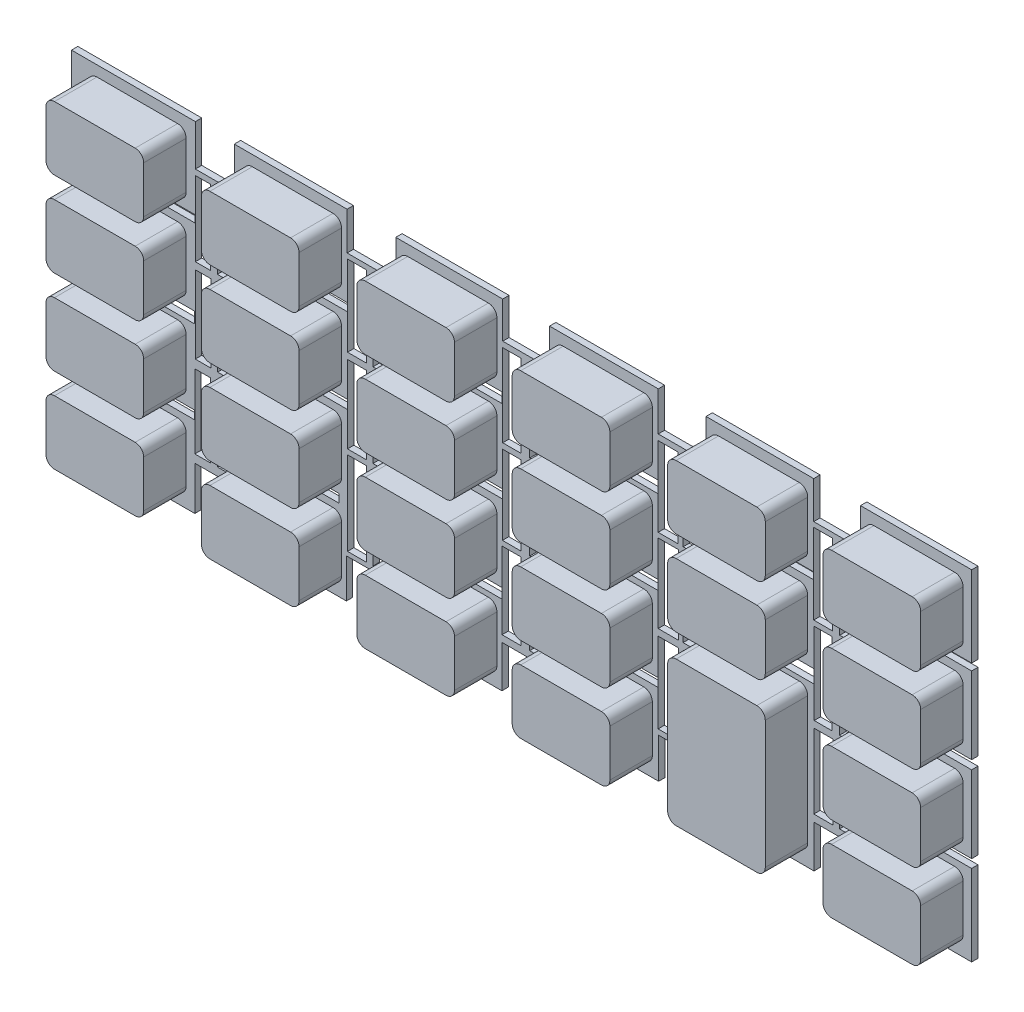
SolidWorks part; units mm, degrees
ref_plane "Front Plane" through (0, 0, 0) normal (0, 0, 1) x (1, 0, 0)
ref_plane "Top Plane" through (0, 0, 0) normal (0, 1, 0) x (1, 0, 0)
ref_plane "Right Plane" through (0, 0, 0) normal (1, 0, 0) x (0, 0, -1)
sketch "Sketch1" plane through (0, 0, 0) normal (0, 0, 1) x (1, 0, 0)
  line L1 (64.5, -22) -> (-64.5, -22)
  line L2 (64.5, -22) -> (64.5, 22)
  line L3 (64.5, 22) -> (-64.5, 22)
  line L4 (-64.5, -22) -> (-64.5, 22)
  line L5 (64.5, -22) -> (-64.5, 22) construction
  line L6 (64.5, 22) -> (-64.5, -22) construction
  point P0 (0, 0)
  dimension "D1" = 129
  dimension "D2" = 44
extrude "main_body" add sketch "Sketch1" along normal blind 0.75
sketch "Sketch2" plane through (0, 0, 0.75) normal (0, 0, 1) x (1, 0, 0)
  line L0 (46.25, 22) -> (46.25, -22) construction
  line L1 (64.5, 22) -> (-64.5, 22) construction
  line L2 (-64.5, -22) -> (64.5, -22) construction
  line L3 (64.5, -22) -> (64.5, 22) construction
  line L4 (36.95, -5) -> (36.95, -15) construction
  line L5 (27.95, -22) -> (27.95, 22) construction
  line L6 (-64.5, 22) -> (-64.5, -22) construction
  line L7 (-39.5, 11.25) -> (-51, 11.25)
  line L8 (9.65, 22) -> (9.65, -22) construction
  line L9 (-39.5, 1.25) -> (-51, 1.25)
  line L10 (64.5, 5) -> (-64.5, 5) construction
  line L11 (-8.65, -22) -> (-8.65, 22) construction
  line L12 (-39.5, 1.25) -> (-39.5, 8.75)
  line L13 (-39.5, 8.75) -> (-51, 8.75)
  line L14 (-26.95, 22) -> (-26.95, -22) construction
  line L15 (-64.5, 15) -> (64.5, 15) construction
  line L16 (-51, 1.25) -> (-51, 8.75)
  line L17 (-45.25, -22) -> (-45.25, 22) construction
  line L18 (-39.5, 1.25) -> (-51, 8.75) construction
  line L19 (64.5, -5) -> (-64.5, -5) construction
  line L20 (-39.5, 8.75) -> (-51, 1.25) construction
  line L21 (-21.2, 1.25) -> (-32.7, 1.25)
  line L22 (-64.5, -15) -> (64.5, -15) construction
  line L23 (-21.2, 1.25) -> (-21.2, 8.75)
  line L24 (-21.2, 8.75) -> (-32.7, 8.75)
  line L25 (-32.7, 1.25) -> (-32.7, 8.75)
  line L26 (-21.2, 1.25) -> (-32.7, 8.75) construction
  line L27 (-21.2, 8.75) -> (-32.7, 1.25) construction
  line L28 (-2.9, 1.25) -> (-14.4, 1.25)
  line L29 (-2.9, 1.25) -> (-2.9, 8.75)
  line L30 (-2.9, 8.75) -> (-14.4, 8.75)
  line L31 (-14.4, 1.25) -> (-14.4, 8.75)
  line L32 (-2.9, 1.25) -> (-14.4, 8.75) construction
  line L33 (-2.9, 8.75) -> (-14.4, 1.25) construction
  line L34 (15.4, 1.25) -> (3.9, 1.25)
  line L35 (15.4, 1.25) -> (15.4, 8.75)
  line L36 (15.4, 8.75) -> (3.9, 8.75)
  line L37 (3.9, 1.25) -> (3.9, 8.75)
  line L38 (15.4, 1.25) -> (3.9, 8.75) construction
  line L39 (15.4, 8.75) -> (3.9, 1.25) construction
  line L40 (33.7, 1.25) -> (22.2, 1.25)
  line L41 (33.7, 1.25) -> (33.7, 8.75)
  line L42 (33.7, 8.75) -> (22.2, 8.75)
  line L43 (22.2, 1.25) -> (22.2, 8.75)
  line L44 (33.7, 1.25) -> (22.2, 8.75) construction
  line L45 (33.7, 8.75) -> (22.2, 1.25) construction
  line L46 (52, -8.75) -> (40.5, -8.75)
  line L47 (52, -8.75) -> (52, -1.25)
  line L48 (52, -1.25) -> (40.5, -1.25)
  line L49 (40.5, -8.75) -> (40.5, -1.25)
  line L50 (52, -8.75) -> (40.5, -1.25) construction
  line L51 (52, -1.25) -> (40.5, -8.75) construction
  line L52 (52, -18.75) -> (40.5, -18.75)
  line L53 (52, -18.75) -> (52, -11.25)
  line L54 (52, -11.25) -> (40.5, -11.25)
  line L55 (40.5, -18.75) -> (40.5, -11.25)
  line L56 (52, -18.75) -> (40.5, -11.25) construction
  line L57 (52, -11.25) -> (40.5, -18.75) construction
  line L58 (52, 11.25) -> (40.5, 11.25)
  line L59 (52, 11.25) -> (52, 18.75)
  line L60 (52, 18.75) -> (40.5, 18.75)
  line L61 (40.5, 11.25) -> (40.5, 18.75)
  line L62 (52, 11.25) -> (40.5, 18.75) construction
  line L63 (52, 18.75) -> (40.5, 11.25) construction
  line L64 (-39.5, 11.25) -> (-39.5, 18.75)
  line L65 (-39.5, 18.75) -> (-51, 18.75)
  line L66 (-51, 11.25) -> (-51, 18.75)
  line L67 (-39.5, 11.25) -> (-51, 18.75) construction
  line L68 (-39.5, 18.75) -> (-51, 11.25) construction
  line L69 (-39.5, -8.75) -> (-51, -8.75)
  line L70 (-39.5, -8.75) -> (-39.5, -1.25)
  line L71 (-39.5, -1.25) -> (-51, -1.25)
  line L72 (-51, -8.75) -> (-51, -1.25)
  line L73 (-39.5, -8.75) -> (-51, -1.25) construction
  line L74 (-39.5, -1.25) -> (-51, -8.75) construction
  line L75 (-39.5, -18.75) -> (-51, -18.75)
  line L76 (-39.5, -18.75) -> (-39.5, -11.25)
  line L77 (-39.5, -11.25) -> (-51, -11.25)
  line L78 (-51, -18.75) -> (-51, -11.25)
  line L79 (-39.5, -18.75) -> (-51, -11.25) construction
  line L80 (-39.5, -11.25) -> (-51, -18.75) construction
  line L81 (-21.2, 11.25) -> (-32.7, 11.25)
  line L82 (-21.2, 11.25) -> (-21.2, 18.75)
  line L83 (-21.2, 18.75) -> (-32.7, 18.75)
  line L84 (-32.7, 11.25) -> (-32.7, 18.75)
  line L85 (-21.2, 11.25) -> (-32.7, 18.75) construction
  line L86 (-21.2, 18.75) -> (-32.7, 11.25) construction
  line L87 (-21.2, -8.75) -> (-32.7, -8.75)
  line L88 (-21.2, -8.75) -> (-21.2, -1.25)
  line L89 (-21.2, -1.25) -> (-32.7, -1.25)
  line L90 (-32.7, -8.75) -> (-32.7, -1.25)
  line L91 (-21.2, -8.75) -> (-32.7, -1.25) construction
  line L92 (-21.2, -1.25) -> (-32.7, -8.75) construction
  line L93 (-21.2, -18.75) -> (-32.7, -18.75)
  line L94 (-21.2, -18.75) -> (-21.2, -11.25)
  line L95 (-21.2, -11.25) -> (-32.7, -11.25)
  line L96 (-32.7, -18.75) -> (-32.7, -11.25)
  line L97 (-21.2, -18.75) -> (-32.7, -11.25) construction
  line L98 (-21.2, -11.25) -> (-32.7, -18.75) construction
  line L99 (-2.9, -8.75) -> (-14.4, -8.75)
  line L100 (-2.9, -8.75) -> (-2.9, -1.25)
  line L101 (-2.9, -1.25) -> (-14.4, -1.25)
  line L102 (-14.4, -8.75) -> (-14.4, -1.25)
  line L103 (-2.9, -8.75) -> (-14.4, -1.25) construction
  line L104 (-2.9, -1.25) -> (-14.4, -8.75) construction
  line L105 (-2.9, -18.75) -> (-14.4, -18.75)
  line L106 (-2.9, -18.75) -> (-2.9, -11.25)
  line L107 (-2.9, -11.25) -> (-14.4, -11.25)
  line L108 (-14.4, -18.75) -> (-14.4, -11.25)
  line L109 (-2.9, -18.75) -> (-14.4, -11.25) construction
  line L110 (-2.9, -11.25) -> (-14.4, -18.75) construction
  line L111 (-2.9, 11.25) -> (-14.4, 11.25)
  line L112 (-2.9, 11.25) -> (-2.9, 18.75)
  line L113 (-2.9, 18.75) -> (-14.4, 18.75)
  line L114 (-14.4, 11.25) -> (-14.4, 18.75)
  line L115 (-2.9, 11.25) -> (-14.4, 18.75) construction
  line L116 (-2.9, 18.75) -> (-14.4, 11.25) construction
  line L117 (15.4, 11.25) -> (3.9, 11.25)
  line L118 (15.4, 11.25) -> (15.4, 18.75)
  line L119 (15.4, 18.75) -> (3.9, 18.75)
  line L120 (3.9, 11.25) -> (3.9, 18.75)
  line L121 (15.4, 11.25) -> (3.9, 18.75) construction
  line L122 (15.4, 18.75) -> (3.9, 11.25) construction
  line L123 (15.4, -8.75) -> (3.9, -8.75)
  line L124 (15.4, -8.75) -> (15.4, -1.25)
  line L125 (15.4, -1.25) -> (3.9, -1.25)
  line L126 (3.9, -8.75) -> (3.9, -1.25)
  line L127 (15.4, -8.75) -> (3.9, -1.25) construction
  line L128 (15.4, -1.25) -> (3.9, -8.75) construction
  line L129 (15.4, -18.75) -> (3.9, -18.75)
  line L130 (15.4, -18.75) -> (15.4, -11.25)
  line L131 (15.4, -11.25) -> (3.9, -11.25)
  line L132 (3.9, -18.75) -> (3.9, -11.25)
  line L133 (15.4, -18.75) -> (3.9, -11.25) construction
  line L134 (15.4, -11.25) -> (3.9, -18.75) construction
  line L135 (33.7, 11.25) -> (22.2, 11.25)
  line L136 (33.7, 11.25) -> (33.7, 18.75)
  line L137 (33.7, 18.75) -> (22.2, 18.75)
  line L138 (22.2, 11.25) -> (22.2, 18.75)
  line L139 (33.7, 11.25) -> (22.2, 18.75) construction
  line L140 (33.7, 18.75) -> (22.2, 11.25) construction
  line L141 (52, 1.25) -> (40.5, 1.25)
  line L142 (52, 1.25) -> (52, 8.75)
  line L143 (52, 8.75) -> (40.5, 8.75)
  line L144 (40.5, 1.25) -> (40.5, 8.75)
  line L145 (52, 1.25) -> (40.5, 8.75) construction
  line L146 (52, 8.75) -> (40.5, 1.25) construction
  line L147 (36.95, -10) -> (27.95, -10) construction
  line L149 (33.7, -18.5) -> (22.2, -18.5)
  line L150 (33.7, -18.5) -> (33.7, -1.5)
  line L151 (33.7, -1.5) -> (22.2, -1.5)
  line L152 (22.2, -18.5) -> (22.2, -1.5)
  line L153 (33.7, -18.5) -> (22.2, -1.5) construction
  line L154 (33.7, -1.5) -> (22.2, -18.5) construction
  point P13 (-45.25, 15)
  point P23 (-45.25, 5)
  point P35 (-26.95, 5)
  point P40 (-8.65, 5)
  point P45 (9.65, 5)
  point P50 (27.95, 5)
  point P55 (46.25, -5)
  point P60 (46.25, -15)
  point P65 (46.25, 15)
  point P70 (-45.25, -5)
  point P75 (-45.25, -15)
  point P80 (-26.95, 15)
  point P88 (-26.95, -5)
  point P93 (-26.95, -15)
  point P98 (-8.65, -15)
  point P100 (-8.65, -5)
  point P108 (-8.65, 15)
  point P113 (9.65, 15)
  point P118 (9.65, -5)
  point P123 (9.65, -15)
  point P128 (27.95, 15)
  point P133 (46.25, 5)
  point P142 (27.95, -10)
  dimension "D1" = 18.25
  dimension "D3" = 18.3
  dimension "D4" = 18.3
  dimension "D5" = 18.3
  dimension "D6" = 18.3
  dimension "D7" = 10
  dimension "D8" = 7
  dimension "D9" = 10
  dimension "D10" = 10
  dimension "D11" = 11.5
  dimension "D12" = 11.5
  dimension "D13" = 11.5
  dimension "D14" = 11.5
  dimension "D15" = 7.5
  dimension "D16" = 7.5
  dimension "D17" = 7.5
  dimension "D18" = 7.5
  dimension "D19" = 7.5
  dimension "D20" = 7.5
  dimension "D21" = 11.5
  dimension "D22" = 11.5
  dimension "D23" = 7.5
  dimension "D24" = 11.5
  dimension "D25" = 11.5
  dimension "D26" = 7.5
  dimension "D27" = 7
  dimension "D28" = 18.3
  dimension "D29" = 19.25
  dimension "D30" = 9
  dimension "D31" = 5
  dimension "D32" = 5
  dimension "D33" = 11.5
  dimension "D34" = 7.5
  dimension "D35" = 11.5
  dimension "D36" = 7.5
  dimension "D37" = 11.5
  dimension "D38" = 7.5
  dimension "D39" = 11.5
  dimension "D40" = 7.5
  dimension "D41" = 11.5
  dimension "D42" = 7.5
  dimension "D43" = 11.5
  dimension "D44" = 7.5
  dimension "D45" = 11.5
  dimension "D46" = 17
  dimension "D47" = 11.5
  dimension "D48" = 7.5
  dimension "D49" = 11.5
  dimension "D50" = 7.5
  dimension "D51" = 11.5
  dimension "D52" = 11.5
  dimension "D53" = 11.5
  dimension "D54" = 11.5
  dimension "D55" = 11.5
  dimension "D56" = 11.5
  dimension "D57" = 7.5
  dimension "D58" = 7.5
  dimension "D59" = 7.5
  dimension "D60" = 7.5
  dimension "D61" = 7.5
  dimension "D62" = 7.5
extrude "button_bumps" add sketch "Sketch2" along normal blind 5
fillet "button_corners" [suppressed] radius 1
fillet "button_top" [suppressed] radius 1
sketch "Sketch3" [suppressed] plane through (0, 0, 5.5) normal (0, 0, 1) x (1, 0, 0)
  line L0 (-50.5, 22) -> (-50.5, -22) construction
  line L1 (61.5, 22) -> (-61.5, 22) construction
  line L2 (-61.5, -22) -> (61.5, -22) construction
  line L3 (-32.2, 22) -> (-32.2, -22) construction
  line L4 (64.5, -19) -> (64.5, 19) construction
  line L5 (-52.25, 14.5) -> (-38.25, 14.5) construction
  line L6 (-52.25, 18) -> (-52.25, 12) construction
  line L7 (-13.9, 22) -> (-13.9, -22) construction
  line L8 (-38.25, 12) -> (-38.25, 18) construction
  line L9 (2.65, -12) -> (2.65, -18) construction
  line L10 (20.95, -2.5) -> (20.95, -17.5) construction
  line L11 (39.25, -12) -> (39.25, -18) construction
  line L12 (-15.65, -12) -> (-15.65, -18) construction
  line L13 (4.4, -22) -> (4.4, 22) construction
  line L14 (-33.95, -12) -> (-33.95, -18) construction
  line L15 (-52.25, -12) -> (-52.25, -18) construction
  line L16 (22.7, 22) -> (22.7, -22) construction
  line L17 (-64.5, 13.5) -> (64.5, 13.5) construction
  line L18 (-64.5, 19) -> (-64.5, -19) construction
  line L19 (41, -22) -> (41, 22) construction
  line L20 (-64.5, 3.5) -> (64.5, 3.5) construction
  line L21 (-52.25, 4.5) -> (-38.25, 4.5) construction
  line L22 (-52.25, 8) -> (-52.25, 2) construction
  line L23 (-64.5, -6.5) -> (64.5, -6.5) construction
  line L24 (-38.25, 2) -> (-38.25, 8) construction
  line L25 (-52.25, -15.5) -> (-38.25, -15.5) construction
  line L26 (64.5, -16.5) -> (-64.5, -16.5) construction
  line L27 (-52.25, -12) -> (-52.25, -18) construction
  line L28 (-38.25, -8) -> (-38.25, -2) construction
  line L29 (-38.25, -5.5) -> (-52.25, -5.5) construction
  line L30 (-52.25, -2) -> (-52.25, -8) construction
  line L31 (-38.25, -18) -> (-38.25, -12) construction
  line L32 (-33.95, 12.5) -> (34.95, 12.5) construction
  line L33 (-33.95, 18) -> (-33.95, 12) construction
  line L34 (34.95, 12) -> (34.95, 18) construction
  line L35 (-33.95, 2.5) -> (34.95, 2.5) construction
  line L36 (-21.35, 19) -> (-21.35, -19) construction
  line L37 (-20.95, 19) -> (-32.95, 19) construction
  line L38 (-33.95, 8) -> (-33.95, 2) construction
  line L39 (34.95, 2) -> (34.95, 8) construction
  line L40 (-32.95, -19) -> (-20.95, -19) construction
  line L41 (-33.95, -7.5) -> (34.95, -7.5) construction
  line L42 (-19.95, -18) -> (-19.95, -12) construction
  line L43 (-33.95, -2) -> (-33.95, -8) construction
  line L44 (34.95, -17.5) -> (34.95, -2.5) construction
  line L45 (-3.05, 19) -> (-3.05, -19) construction
  line L46 (-33.95, -17.5) -> (34.95, -17.5) construction
  line L47 (-2.65, 19) -> (-14.65, 19) construction
  line L48 (-14.65, -19) -> (-2.65, -19) construction
  line L49 (-33.95, -12) -> (-33.95, -18) construction
  line L50 (-33.95, 15.3) -> (34.95, 15.3) construction
  line L51 (-33.95, 5.3) -> (34.95, 5.3) construction
  line L52 (-33.95, -4.7) -> (34.95, -4.7) construction
  line L53 (-33.95, -14.7) -> (34.95, -14.7) construction
  line L54 (-1.65, -18) -> (-1.65, -12) construction
  line L55 (-4.6, -14.55) -> (-3.2, -14.55)
  line L56 (15.25, 19) -> (15.25, -19) construction
  line L57 (-3.05, -14.7) -> (-4.75, -14.7)
  line L58 (15.65, 19) -> (3.65, 19) construction
  line L59 (-3.05, -14.7) -> (-3.05, -14.55)
  line L60 (3.65, -19) -> (15.65, -19) construction
  line L62 (33.55, 19) -> (33.55, -18.5) construction
  line L63 (33.95, 19) -> (21.95, 19) construction
  line L64 (21.95, -18.5) -> (33.95, -18.5) construction
  line L65 (16.65, -18) -> (16.65, -12) construction
  line L66 (34.95, -17.5) -> (34.95, -2.5) construction
  line L67 (-4.75, -14.7) -> (-4.75, -14.55)
  line L69 (-4.75, -14.55) -> (-4.75, -14.4)
  line L70 (-4.75, -14.4) -> (-4.6, -14.4)
  line L71 (-4.6, -14.55) -> (-4.6, -14.4)
  line L73 (-3.05, -14.55) -> (-3.05, -14.4)
  line L74 (-3.05, -14.4) -> (-3.2, -14.4)
  line L75 (-3.2, -14.55) -> (-3.2, -14.4)
  line L76 (39.25, 13.8) -> (53.25, 13.8) construction
  line L77 (39.25, 18) -> (39.25, 12) construction
  line L78 (53.25, 12) -> (53.25, 18) construction
  line L79 (39.25, 3.8) -> (53.25, 3.8) construction
  line L80 (39.25, 8) -> (39.25, 2) construction
  line L81 (53.25, 2) -> (53.25, 8) construction
  line L82 (39.25, -6.2) -> (53.25, -6.2) construction
  line L83 (39.25, -2) -> (39.25, -8) construction
  line L84 (53.25, -8) -> (53.25, -2) construction
  line L85 (39.25, -16.2) -> (53.25, -16.2) construction
  line L86 (39.25, -12) -> (39.25, -18) construction
  line L87 (53.25, -18) -> (53.25, -12) construction
  line L88 (-52.25, 12.5) -> (-38.25, 12.5) construction
  line L89 (-52.25, 18) -> (-52.25, 12) construction
  line L90 (-38.25, 12) -> (-38.25, 18) construction
  line L91 (-52.25, 2.5) -> (-38.25, 2.5) construction
  line L92 (-52.25, -7.5) -> (-38.25, -7.5) construction
  line L93 (-52.25, -17.5) -> (-38.25, -17.5) construction
  text T0 "1" font "Arial Narrow" height in points 14
  text T1 "SSB" font "Arial Narrow" height in points 10
  text T2 "4" font "Arial Narrow" height in points 14
  text T3 "2" font "Arial Narrow" height in points 14
  text T4 "3" font "Arial Narrow" height in points 14
  text T5 "5" font "Arial Narrow" height in points 14
  text T6 "6" font "Arial Narrow" height in points 14
  text T7 "7" font "Arial Narrow" height in points 14
  text T8 "8" font "Arial Narrow" height in points 14
  text T9 "9" font "Arial Narrow" height in points 14
  text T10 "." font "Arial Rounded MT Bold" height in points 14
  text T11 "0" font "Arial Narrow" height in points 14
  text T12 "C" font "Arial Narrow" height in points 14
  text T13 "M" font "Arial Narrow" height in points 14
  text T14 "S" font "Arial Narrow" height in points 14
  text T15 "CW" font "Arial Narrow" height in points 10
  text T16 "AM" font "Arial Narrow" height in points 10
  text T17 "FIX" font "Arial Narrow" height in points 10
  text T18 "             160m" font "Arial Narrow" height in points 6
  text T19 "               30m" font "Arial Narrow" height in points 6
  text T20 "               12m" font "Arial Narrow" height in points 6
  text T21 "                 4m" font "Arial Narrow" height in points 6
  text T22 "               80m" font "Arial Narrow" height in points 6
  text T23 "               20m" font "Arial Narrow" height in points 6
  text T24 "               10m" font "Arial Narrow" height in points 6
  text T25 "                  LF" font "Arial Narrow" height in points 6
  text T26 "               60m" font "Arial Narrow" height in points 6
  text T27 "               17m" font "Arial Narrow" height in points 6
  text T28 "                 6m" font "Arial Narrow" height in points 6
  text T29 "                 MF" font "Arial Narrow" height in points 6
  text T30 "               40m" font "Arial Narrow" height in points 6
  text T31 "               15m" font "Arial Narrow" height in points 6
  text T32 "          ENTER" font "Arial Narrow" height in points 6
  text T33 "           ABC" font "Arial Narrow" height in points 7
  text T34 "           DEF" font "Arial Narrow" height in points 7
  text T35 "            GHI" font "Arial Narrow" height in points 7
  text T36 "             JKL" font "Arial Narrow" height in points 7
  text T37 "          MNO" font "Arial Narrow" height in points 7
  text T38 "         PQRS" font "Arial Narrow" height in points 7
  text T39 "           TUV" font "Arial Narrow" height in points 7
  text T40 "        WXYZ" font "Arial Narrow" height in points 7
  text T41 "              */--" font "Arial Narrow" height in points 7
  text T42 "         ↵" font "Lucida Sans Unicode" height in points 7
  text T43 "   DSP" font "Arial Narrow" height in points 10
  text T44 "  STEP" font "Arial Narrow" height in points 10
  text T45 "FILTER" font "Arial Narrow" height in points 10
  text T46 "  SPLIT" font "Arial Narrow" height in points 10
  text T47 "                   LSB/USB" font "Arial Narrow" height in points 4
  text T48 "                      KEYER" font "Arial Narrow" height in points 4
  text T49 "                    FM/DIGI" font "Arial Narrow" height in points 4
  text T50 "                   CENTER" font "Arial Narrow" height in points 4
  dimension "D1" = 23.5
  dimension "D2" = 18.3
  dimension "D3" = 18.3
  dimension "D4" = 18.3
  dimension "D5" = 18.3
  dimension "D6" = 18.3
  dimension "D7" = 1.75
  dimension "D8" = 1.75
  dimension "D9" = 1.75
  dimension "D10" = 1.75
  dimension "D11" = 1.75
  dimension "D12" = 1.75
  dimension "D13" = 10
  dimension "D14" = 10
  dimension "D15" = 10
  dimension "D16" = 8.5
  dimension "D17" = 5.5
  dimension "D18" = 1
  dimension "D19" = 1
  dimension "D20" = 1
  dimension "D21" = 1
  dimension "D22" = 1
  dimension "D23" = 1
  dimension "D24" = 1
  dimension "D25" = 1
  dimension "D26" = 1.8
  dimension "D27" = 1.8
  dimension "D28" = 1.8
  dimension "D29" = 1.8
  dimension "D30" = 1.4
  dimension "D31" = 1.4
  dimension "D32" = 1.4
  dimension "D33" = 1.4
  dimension "D34" = 1.7
  dimension "D35" = 0.15
  dimension "D36" = 0.3
  dimension "D37" = 0.15
  dimension "D38" = 0.15
  dimension "D39" = 0.15
  dimension "D40" = 0.15
  dimension "D41" = 0.15
  dimension "D42" = 0.15
  dimension "D43" = 0.3
  dimension "D44" = 0.3
  dimension "D45" = 0.3
  dimension "D46" = 1
  dimension "D47" = 1
  dimension "D48" = 1
  dimension "D49" = 1
extrude "buttons_text" [suppressed] add sketch "Sketch3" along normal blind 0.1
sketch "Sketch5" plane through (0, 0, 0.75) normal (0, 0, 1) x (1, 0, 0)
  line L62 (-53, 20) -> (53, 20)
  line L63 (-53, 20) -> (-53, -20)
  line L64 (-53, -20) -> (53, -20)
  line L65 (53, 20) -> (53, -20)
  dimension "D1" = 106
  dimension "D2" = 40
  dimension "D3" = 20
  dimension "D4" = 53
extrude "corners_cut" cut sketch "Sketch5" against normal through all flip side to cut
sketch "Sketch6" plane through (0, 0, 0.75) normal (0, 0, 1) x (1, 0, 0)
  line L0 (-53, 20) -> (-53, -20) construction
  line L1 (-53, 10.487) -> (-38.4318, 10.487)
  line L2 (-53, 10.487) -> (-53, 9.639)
  line L3 (-53, 9.639) -> (-38.4318, 9.639)
  line L4 (-38.4318, 10.487) -> (-38.4318, 9.639)
  line L5 (53, 20) -> (-53, 20) construction
  line L6 (-53, 0.6278) -> (-38.5268, 0.6278)
  line L7 (-53, 0.6278) -> (-53, -0.6772)
  line L8 (-53, -0.6772) -> (-38.5268, -0.6772)
  line L9 (-38.5268, 0.6278) -> (-38.5268, -0.6772)
  line L10 (-53, -9.4645) -> (-38.4947, -9.4645)
  line L11 (-53, -9.4645) -> (-53, -10.4595)
  line L12 (-53, -10.4595) -> (-38.4947, -10.4595)
  line L13 (-38.4947, -9.4645) -> (-38.4947, -10.4595)
  line L14 (-38.4124, 20) -> (-33.8283, 20)
  line L15 (-38.4124, 20) -> (-38.4124, 15.1621)
  line L16 (-38.4124, 15.1621) -> (-33.8283, 15.1621)
  line L17 (-33.8283, 20) -> (-33.8283, 15.1621)
  line L18 (-53, -20) -> (53, -20) construction
  line L23 (53, -20) -> (53, 20) construction
  line L24 (-20.5465, 20) -> (-14.8109, 20)
  line L25 (-20.5465, 20) -> (-20.5465, 15.5362)
  line L26 (-20.5465, 15.5362) -> (-14.8109, 15.5362)
  line L27 (-14.8109, 20) -> (-14.8109, 15.5362)
  line L28 (-2.2207, 20) -> (3.2938, 20)
  line L29 (-2.2207, 20) -> (-2.2207, 15.7023)
  line L30 (-2.2207, 15.7023) -> (3.2938, 15.7023)
  line L31 (3.2938, 20) -> (3.2938, 15.7023)
  line L32 (16.0959, 20) -> (21.7218, 20)
  line L33 (16.0959, 20) -> (16.0959, 15.3985)
  line L34 (16.0959, 15.3985) -> (21.7218, 15.3985)
  line L35 (21.7218, 20) -> (21.7218, 15.3985)
  line L36 (34.4017, 20) -> (39.911, 20)
  line L37 (34.4017, 20) -> (34.4017, 15.6134)
  line L38 (34.4017, 15.6134) -> (39.911, 15.6134)
  line L39 (39.911, 20) -> (39.911, 15.6134)
  line L40 (-20.6305, -20) -> (-15.0655, -20)
  line L41 (-20.6305, -20) -> (-20.6305, -15.3916)
  line L42 (-20.6305, -15.3916) -> (-15.0655, -15.3916)
  line L43 (-15.0655, -20) -> (-15.0655, -15.3916)
  line L44 (-2.3118, -20) -> (3.1497, -20)
  line L45 (-2.3118, -20) -> (-2.3118, -15.0585)
  line L46 (-2.3118, -15.0585) -> (3.1497, -15.0585)
  line L47 (3.1497, -20) -> (3.1497, -15.0585)
  line L48 (16.1416, -20) -> (21.3808, -20)
  line L49 (16.1416, -20) -> (16.1416, -15.2957)
  line L50 (16.1416, -15.2957) -> (21.3808, -15.2957)
  line L51 (21.3808, -20) -> (21.3808, -15.2957)
  line L52 (34.4363, -20) -> (39.9725, -20)
  line L53 (34.4363, -20) -> (34.4363, -15.0209)
  line L54 (34.4363, -15.0209) -> (39.9725, -15.0209)
  line L55 (39.9725, -20) -> (39.9725, -15.0209)
  line L61 (53, 0.6278) -> (40.0214, 0.6278)
  line L62 (53, 0.6278) -> (53, -0.4027)
  line L63 (53, -0.4027) -> (40.0214, -0.4027)
  line L64 (40.0214, 0.6278) -> (40.0214, -0.4027)
  line L65 (53, 10.487) -> (39.968, 10.487)
  line L66 (53, 10.487) -> (53, 9.6837)
  line L67 (53, 9.6837) -> (39.968, 9.6837)
  line L68 (39.968, 10.487) -> (39.968, 9.6837)
  line L73 (-38.4124, 14.5006) -> (-36.6167, 14.5006)
  line L74 (-38.4124, 14.5006) -> (-38.4124, 5.7068)
  line L75 (-38.4124, 5.7068) -> (-36.6167, 5.7068)
  line L76 (-36.6167, 14.5006) -> (-36.6167, 5.7068)
  line L81 (-38.4755, -13.9249) -> (-36.6481, -13.9249)
  line L82 (-38.4755, -13.9249) -> (-38.4755, -5.2376)
  line L83 (-38.4755, -5.2376) -> (-36.6481, -5.2376)
  line L84 (-36.6481, -13.9249) -> (-36.6481, -5.2376)
  line L97 (-38.4237, 4.89) -> (-36.5843, 4.89)
  line L98 (-38.4237, 4.89) -> (-38.4237, -4.2234)
  line L99 (-38.4237, -4.2234) -> (-36.5843, -4.2234)
  line L100 (-36.5843, 4.89) -> (-36.5843, -4.2234)
  line L101 (-35.7933, 4.8665) -> (-33.5064, 4.8665)
  line L102 (-35.7933, 4.8665) -> (-35.7933, -4.2413)
  line L103 (-35.7933, -4.2413) -> (-33.5064, -4.2413)
  line L104 (-33.5064, 4.8665) -> (-33.5064, -4.2413)
  line L105 (-33.819, 10.487) -> (-20.5046, 10.487)
  line L106 (-33.819, 10.487) -> (-33.819, 9.5573)
  line L107 (-33.819, 9.5573) -> (-20.5046, 9.5573)
  line L108 (-20.5046, 10.487) -> (-20.5046, 9.5573)
  line L109 (-33.4426, 0.6278) -> (-20.5096, 0.6278)
  line L110 (-33.4426, 0.6278) -> (-33.4426, -0.4027)
  line L111 (-33.4426, -0.4027) -> (-20.5096, -0.4027)
  line L112 (-20.5096, 0.6278) -> (-20.5096, -0.4027)
  line L113 (-33.5346, -9.4645) -> (-21.4766, -9.4645)
  line L114 (-33.5346, -9.4645) -> (-33.5346, -10.4595)
  line L115 (-33.5346, -10.4595) -> (-21.4766, -10.4595)
  line L116 (-21.4766, -9.4645) -> (-21.4766, -10.4595)
  line L117 (-14.7699, 10.487) -> (-2.2829, 10.487)
  line L118 (-14.7699, 10.487) -> (-14.7699, 9.3006)
  line L119 (-14.7699, 9.3006) -> (-2.2829, 9.3006)
  line L120 (-2.2829, 10.487) -> (-2.2829, 9.3006)
  line L121 (-14.8344, 0.6278) -> (-2.2687, 0.6278)
  line L122 (-14.8344, 0.6278) -> (-14.8344, -0.4027)
  line L123 (-14.8344, -0.4027) -> (-2.2687, -0.4027)
  line L124 (-2.2687, 0.6278) -> (-2.2687, -0.4027)
  line L125 (-14.8364, -9.4645) -> (-2.3087, -9.4645)
  line L126 (-14.8364, -9.4645) -> (-14.8364, -10.6477)
  line L127 (-14.8364, -10.6477) -> (-2.3087, -10.6477)
  line L128 (-2.3087, -9.4645) -> (-2.3087, -10.6477)
  line L141 (21.7364, 10.487) -> (34.3679, 10.487)
  line L142 (21.7364, 10.487) -> (21.7364, 9.6837)
  line L143 (21.7364, 9.6837) -> (34.3679, 9.6837)
  line L144 (34.3679, 10.487) -> (34.3679, 9.6837)
  line L149 (53.0113, -9.4645) -> (40.0275, -9.4645)
  line L150 (53.0113, -9.4645) -> (53.0113, -10.4595)
  line L151 (53.0113, -10.4595) -> (40.0275, -10.4595)
  line L152 (40.0275, -9.4645) -> (40.0275, -10.4595)
  line L153 (37.4431, 4.8871) -> (40.011, 4.8871)
  line L154 (37.4431, 4.8871) -> (37.4431, -4.6496)
  line L155 (37.4431, -4.6496) -> (40.011, -4.6496)
  line L156 (40.011, 4.8871) -> (40.011, -4.6496)
  line L157 (37.4599, 15.0198) -> (39.9551, 15.0198)
  line L158 (37.4599, 15.0198) -> (37.4599, 5.552)
  line L159 (37.4599, 5.552) -> (39.9551, 5.552)
  line L160 (39.9551, 15.0198) -> (39.9551, 5.552)
  line L161 (19.0294, 14.7329) -> (21.7058, 14.7329)
  line L162 (19.0294, 14.7329) -> (19.0294, 5.3578)
  line L163 (19.0294, 5.3578) -> (21.7058, 5.3578)
  line L164 (21.7058, 14.7329) -> (21.7058, 5.3578)
  line L165 (16.0811, 4.7899) -> (18.4829, 4.7899)
  line L166 (16.0811, 4.7899) -> (16.0811, -4.4502)
  line L167 (16.0811, -4.4502) -> (18.4829, -4.4502)
  line L168 (18.4829, 4.7899) -> (18.4829, -4.4502)
  line L169 (-2.2558, 4.6853) -> (-0.0559, 4.6853)
  line L170 (-2.2558, 4.6853) -> (-2.2558, -4.6264)
  line L171 (-2.2558, -4.6264) -> (-0.0559, -4.6264)
  line L172 (-0.0559, 4.6853) -> (-0.0559, -4.6264)
  line L173 (0.9534, 15.067) -> (3.3538, 15.067)
  line L174 (0.9534, 15.067) -> (0.9534, 5.3765)
  line L175 (0.9534, 5.3765) -> (3.3538, 5.3765)
  line L176 (3.3538, 15.067) -> (3.3538, 5.3765)
  line L177 (-20.4967, 4.7067) -> (-18.255, 4.7067)
  line L178 (-20.4967, 4.7067) -> (-20.4967, -4.4194)
  line L179 (-20.4967, -4.4194) -> (-18.255, -4.4194)
  line L180 (-18.255, 4.7067) -> (-18.255, -4.4194)
  line L181 (-17.508, 14.9557) -> (-14.7882, 14.9557)
  line L182 (-17.508, 14.9557) -> (-17.508, 5.4415)
  line L183 (-17.508, 5.4415) -> (-14.7882, 5.4415)
  line L184 (-14.7882, 14.9557) -> (-14.7882, 5.4415)
  line L185 (34.4168, -5.4308) -> (36.6803, -5.4308)
  line L186 (34.4168, -5.4308) -> (34.4168, -14.2037)
  line L187 (34.4168, -14.2037) -> (36.6803, -14.2037)
  line L188 (36.6803, -5.4308) -> (36.6803, -14.2037)
  line L189 (34.4585, 4.972) -> (36.5623, 4.972)
  line L190 (34.4585, 4.972) -> (34.4585, -4.6433)
  line L191 (34.4585, -4.6433) -> (36.5623, -4.6433)
  line L192 (36.5623, 4.972) -> (36.5623, -4.6433)
  line L193 (34.4017, 15.0307) -> (36.5971, 15.0307)
  line L194 (34.4017, 15.0307) -> (34.4017, 5.5725)
  line L195 (34.4017, 5.5725) -> (36.5971, 5.5725)
  line L196 (36.5971, 15.0307) -> (36.5971, 5.5725)
  line L197 (16.0847, 5.3628) -> (18.452, 5.3628)
  line L198 (16.0847, 5.3628) -> (16.0847, 14.7218)
  line L199 (16.0847, 14.7218) -> (18.452, 14.7218)
  line L200 (18.452, 5.3628) -> (18.452, 14.7218)
  line L201 (-2.2207, 15.0439) -> (-0.0452, 15.0439)
  line L202 (-2.2207, 15.0439) -> (-2.2207, 5.3424)
  line L203 (-2.2207, 5.3424) -> (-0.0452, 5.3424)
  line L204 (-0.0452, 15.0439) -> (-0.0452, 5.3424)
  line L205 (-20.4922, 14.9466) -> (-18.2555, 14.9466)
  line L206 (-20.4922, 14.9466) -> (-20.4922, 5.4415)
  line L207 (-20.4922, 5.4415) -> (-18.2555, 5.4415)
  line L208 (-18.2555, 14.9466) -> (-18.2555, 5.4415)
  line L209 (-17.5036, 4.7276) -> (-14.8461, 4.7276)
  line L210 (-17.5036, 4.7276) -> (-17.5036, -4.4171)
  line L211 (-17.5036, -4.4171) -> (-14.8461, -4.4171)
  line L212 (-14.8461, 4.7276) -> (-14.8461, -4.4171)
  line L213 (-2.299, -5.2268) -> (-0.0558, -5.2268)
  line L214 (-2.299, -5.2268) -> (-2.299, -14.2741)
  line L215 (-2.299, -14.2741) -> (-0.0558, -14.2741)
  line L216 (-0.0558, -5.2268) -> (-0.0558, -14.2741)
  line L217 (19.0218, 4.7331) -> (21.7578, 4.7331)
  line L218 (19.0218, 4.7331) -> (19.0218, -4.415)
  line L219 (19.0218, -4.415) -> (21.7578, -4.415)
  line L220 (21.7578, 4.7331) -> (21.7578, -4.415)
  line L221 (-35.8236, 14.5006) -> (-33.8283, 14.5006)
  line L222 (-35.8236, 14.5006) -> (-35.8236, 5.7204)
  line L223 (-35.8236, 5.7204) -> (-33.8283, 5.7204)
  line L224 (-33.8283, 14.5006) -> (-33.8283, 5.7204)
  line L225 (-35.7933, -5.3926) -> (-33.5611, -5.3926)
  line L226 (-35.7933, -5.3926) -> (-35.7933, -13.9249)
  line L227 (-35.7933, -13.9249) -> (-33.5611, -13.9249)
  line L228 (-33.5611, -5.3926) -> (-33.5611, -13.9249)
  line L229 (-33.5503, -20.001) -> (-38.4755, -20.001)
  line L230 (-33.5503, -20.001) -> (-33.5503, -14.8705)
  line L231 (-33.5503, -14.8705) -> (-38.4755, -14.8705)
  line L232 (-38.4755, -20.001) -> (-38.4755, -14.8705)
  line L237 (-20.4967, -5.0185) -> (-18.255, -5.0185)
  line L238 (-20.4967, -5.0185) -> (-20.4967, -14.8705)
  line L239 (-20.4967, -14.8705) -> (-18.255, -14.8705)
  line L240 (-18.255, -5.0185) -> (-18.255, -14.8705)
  line L241 (-17.5036, -5.0185) -> (-14.8461, -5.0185)
  line L242 (-17.5036, -5.0185) -> (-17.5036, -14.8705)
  line L243 (-17.5036, -14.8705) -> (-14.8461, -14.8705)
  line L244 (-14.8461, -5.0185) -> (-14.8461, -14.8705)
  line L245 (0.9534, 4.3611) -> (3.3538, 4.3611)
  line L246 (0.9534, 4.3611) -> (0.9534, -4.6264)
  line L247 (0.9534, -4.6264) -> (3.3538, -4.6264)
  line L248 (3.3538, 4.3611) -> (3.3538, -4.6264)
  line L249 (0.9534, -5.2268) -> (3.2938, -5.2268)
  line L250 (0.9534, -5.2268) -> (0.9534, -14.2741)
  line L251 (0.9534, -14.2741) -> (3.2938, -14.2741)
  line L252 (3.2938, -5.2268) -> (3.2938, -14.2741)
  line L253 (3.3634, 10.6849) -> (16.0701, 10.6849)
  line L254 (3.3634, 10.6849) -> (3.3634, 9.2912)
  line L255 (3.3634, 9.2912) -> (16.0701, 9.2912)
  line L256 (16.0701, 10.6849) -> (16.0701, 9.2912)
  line L261 (3.3694, 0.5495) -> (16.0509, 0.5495)
  line L262 (3.3694, 0.5495) -> (3.3694, -0.5761)
  line L263 (3.3694, -0.5761) -> (16.0509, -0.5761)
  line L264 (16.0509, 0.5495) -> (16.0509, -0.5761)
  line L269 (3.3073, -9.4645) -> (16.0753, -9.4645)
  line L270 (3.3073, -9.4645) -> (3.3073, -10.4595)
  line L271 (3.3073, -10.4595) -> (16.0753, -10.4595)
  line L272 (16.0753, -9.4645) -> (16.0753, -10.4595)
  line L277 (16.0811, -5.2268) -> (18.4829, -5.2268)
  line L278 (16.0811, -5.2268) -> (16.0811, -14.6884)
  line L279 (16.0811, -14.6884) -> (18.4829, -14.6884)
  line L280 (18.4829, -5.2268) -> (18.4829, -14.6884)
  line L281 (19.0218, -5.2368) -> (21.7578, -5.2368)
  line L282 (19.0218, -5.2368) -> (19.0218, -14.6884)
  line L283 (19.0218, -14.6884) -> (21.7578, -14.6884)
  line L284 (21.7578, -5.2368) -> (21.7578, -14.6884)
  line L289 (21.7852, 0.6278) -> (34.4327, 0.6278)
  line L290 (21.7852, 0.6278) -> (21.7852, -0.9337)
  line L291 (21.7852, -0.9337) -> (34.4327, -0.9337)
  line L292 (34.4327, 0.6278) -> (34.4327, -0.9337)
  line L293 (37.4431, -5.5236) -> (40.011, -5.5236)
  line L294 (37.4431, -5.5236) -> (37.4431, -14.2037)
  line L295 (37.4431, -14.2037) -> (40.011, -14.2037)
  line L296 (40.011, -5.5236) -> (40.011, -14.2037)
extrude "inkeys_cut" cut sketch "Sketch6" against normal through all
sketch "Sketch7" plane through (0, 0, 5.75) normal (0, 0, 1) x (1, 0, 0)
  line L0 (52, -15) -> (-51, -15) construction
  line L1 (52, -18.75) -> (52, -11.25) construction
  line L2 (-51, -11.25) -> (-51, -18.75) construction
  line L3 (-26.95, -18.75) -> (-26.95, 18.75) construction
  line L4 (52, -8.75) -> (52, -1.25) construction
  line L5 (52, -5) -> (-51, -5) construction
  line L6 (-51, -1.25) -> (-51, -8.75) construction
  line L7 (-32.7, -18.75) -> (-21.2, -18.75) construction
  line L8 (52, 1.25) -> (52, 8.75) construction
  line L9 (52, 5) -> (-51, 5) construction
  line L10 (-51, 8.75) -> (-51, 1.25) construction
  line L11 (-21.2, 18.75) -> (-32.7, 18.75) construction
  line L12 (52, 11.25) -> (52, 18.75) construction
  line L13 (52, 15) -> (-51, 15) construction
  line L14 (-51, 18.75) -> (-51, 11.25) construction
  line L15 (27.95, -18.5) -> (27.95, 18.75) construction
  line L16 (-39.5, 18.75) -> (-51, 18.75) construction
  line L17 (-45.25, 18.75) -> (-45.25, -18.75) construction
  line L18 (-51, -18.75) -> (-39.5, -18.75) construction
  line L19 (22.2, -18.5) -> (33.7, -18.5) construction
  line L21 (33.7, 18.75) -> (22.2, 18.75) construction
  line L23 (22.2, -10) -> (33.7, -10) construction
  line L24 (-2.9, 18.75) -> (-14.4, 18.75) construction
  line L25 (-8.65, 18.75) -> (-8.65, -18.75) construction
  line L26 (-14.4, -18.75) -> (-2.9, -18.75) construction
  line L28 (15.4, 18.75) -> (3.9, 18.75) construction
  line L29 (9.65, 18.75) -> (9.65, -18.75) construction
  line L30 (3.9, -18.75) -> (15.4, -18.75) construction
  line L34 (22.2, -1.5) -> (22.2, -18.5) construction
  line L35 (52, 18.75) -> (40.5, 18.75) construction
  line L36 (46.25, 18.75) -> (46.25, -18.75) construction
  line L37 (40.5, -18.75) -> (52, -18.75) construction
  line L38 (33.7, -18.5) -> (33.7, -1.5) construction
  line L39 (-41.875, 11.625) -> (-48.625, 11.625)
  line L40 (-41.875, 11.625) -> (-41.875, 18.375)
  line L41 (-41.875, 18.375) -> (-48.625, 18.375)
  line L42 (-48.625, 11.625) -> (-48.625, 18.375)
  line L43 (-41.875, 11.625) -> (-48.625, 18.375) construction
  line L44 (-41.875, 18.375) -> (-48.625, 11.625) construction
  line L45 (-41.875, 1.625) -> (-48.625, 1.625)
  line L46 (-41.875, 1.625) -> (-41.875, 8.375)
  line L47 (-41.875, 8.375) -> (-48.625, 8.375)
  line L48 (-48.625, 1.625) -> (-48.625, 8.375)
  line L49 (-41.875, 1.625) -> (-48.625, 8.375) construction
  line L50 (-41.875, 8.375) -> (-48.625, 1.625) construction
  line L51 (-41.875, -8.375) -> (-48.625, -8.375)
  line L52 (-41.875, -8.375) -> (-41.875, -1.625)
  line L53 (-41.875, -1.625) -> (-48.625, -1.625)
  line L54 (-48.625, -8.375) -> (-48.625, -1.625)
  line L55 (-41.875, -8.375) -> (-48.625, -1.625) construction
  line L56 (-41.875, -1.625) -> (-48.625, -8.375) construction
  line L57 (-41.875, -18.375) -> (-48.625, -18.375)
  line L58 (-41.875, -18.375) -> (-41.875, -11.625)
  line L59 (-41.875, -11.625) -> (-48.625, -11.625)
  line L60 (-48.625, -18.375) -> (-48.625, -11.625)
  line L61 (-41.875, -18.375) -> (-48.625, -11.625) construction
  line L62 (-41.875, -11.625) -> (-48.625, -18.375) construction
  line L63 (-23.575, 11.625) -> (-30.325, 11.625)
  line L64 (-23.575, 11.625) -> (-23.575, 18.375)
  line L65 (-23.575, 18.375) -> (-30.325, 18.375)
  line L66 (-30.325, 11.625) -> (-30.325, 18.375)
  line L67 (-23.575, 11.625) -> (-30.325, 18.375) construction
  line L68 (-23.575, 18.375) -> (-30.325, 11.625) construction
  line L69 (-23.575, 1.625) -> (-30.325, 1.625)
  line L70 (-23.575, 1.625) -> (-23.575, 8.375)
  line L71 (-23.575, 8.375) -> (-30.325, 8.375)
  line L72 (-30.325, 1.625) -> (-30.325, 8.375)
  line L73 (-23.575, 1.625) -> (-30.325, 8.375) construction
  line L74 (-23.575, 8.375) -> (-30.325, 1.625) construction
  line L75 (-23.575, -8.375) -> (-30.325, -8.375)
  line L76 (-23.575, -8.375) -> (-23.575, -1.625)
  line L77 (-23.575, -1.625) -> (-30.325, -1.625)
  line L78 (-30.325, -8.375) -> (-30.325, -1.625)
  line L79 (-23.575, -8.375) -> (-30.325, -1.625) construction
  line L80 (-23.575, -1.625) -> (-30.325, -8.375) construction
  line L81 (-23.575, -18.375) -> (-30.325, -18.375)
  line L82 (-23.575, -18.375) -> (-23.575, -11.625)
  line L83 (-23.575, -11.625) -> (-30.325, -11.625)
  line L84 (-30.325, -18.375) -> (-30.325, -11.625)
  line L85 (-23.575, -18.375) -> (-30.325, -11.625) construction
  line L86 (-23.575, -11.625) -> (-30.325, -18.375) construction
  line L87 (-5.275, 11.625) -> (-12.025, 11.625)
  line L88 (-5.275, 11.625) -> (-5.275, 18.375)
  line L89 (-5.275, 18.375) -> (-12.025, 18.375)
  line L90 (-12.025, 11.625) -> (-12.025, 18.375)
  line L91 (-5.275, 11.625) -> (-12.025, 18.375) construction
  line L92 (-5.275, 18.375) -> (-12.025, 11.625) construction
  line L93 (-5.275, 1.625) -> (-12.025, 1.625)
  line L94 (-5.275, 1.625) -> (-5.275, 8.375)
  line L95 (-5.275, 8.375) -> (-12.025, 8.375)
  line L96 (-12.025, 1.625) -> (-12.025, 8.375)
  line L97 (-5.275, 1.625) -> (-12.025, 8.375) construction
  line L98 (-5.275, 8.375) -> (-12.025, 1.625) construction
  line L99 (-5.275, -8.375) -> (-12.025, -8.375)
  line L100 (-5.275, -8.375) -> (-5.275, -1.625)
  line L101 (-5.275, -1.625) -> (-12.025, -1.625)
  line L102 (-12.025, -8.375) -> (-12.025, -1.625)
  line L103 (-5.275, -8.375) -> (-12.025, -1.625) construction
  line L104 (-5.275, -1.625) -> (-12.025, -8.375) construction
  line L105 (-5.275, -18.375) -> (-12.025, -18.375)
  line L106 (-5.275, -18.375) -> (-5.275, -11.625)
  line L107 (-5.275, -11.625) -> (-12.025, -11.625)
  line L108 (-12.025, -18.375) -> (-12.025, -11.625)
  line L109 (-5.275, -18.375) -> (-12.025, -11.625) construction
  line L110 (-5.275, -11.625) -> (-12.025, -18.375) construction
  line L111 (13.025, -18.375) -> (6.275, -18.375)
  line L112 (13.025, -18.375) -> (13.025, -11.625)
  line L113 (13.025, -11.625) -> (6.275, -11.625)
  line L114 (6.275, -18.375) -> (6.275, -11.625)
  line L115 (13.025, -18.375) -> (6.275, -11.625) construction
  line L116 (13.025, -11.625) -> (6.275, -18.375) construction
  line L117 (13.025, -8.375) -> (6.275, -8.375)
  line L118 (13.025, -8.375) -> (13.025, -1.625)
  line L119 (13.025, -1.625) -> (6.275, -1.625)
  line L120 (6.275, -8.375) -> (6.275, -1.625)
  line L121 (13.025, -8.375) -> (6.275, -1.625) construction
  line L122 (13.025, -1.625) -> (6.275, -8.375) construction
  line L123 (13.025, 1.625) -> (6.275, 1.625)
  line L124 (13.025, 1.625) -> (13.025, 8.375)
  line L125 (13.025, 8.375) -> (6.275, 8.375)
  line L126 (6.275, 1.625) -> (6.275, 8.375)
  line L127 (13.025, 1.625) -> (6.275, 8.375) construction
  line L128 (13.025, 8.375) -> (6.275, 1.625) construction
  line L129 (13.025, 11.625) -> (6.275, 11.625)
  line L130 (13.025, 11.625) -> (13.025, 18.375)
  line L131 (13.025, 18.375) -> (6.275, 18.375)
  line L132 (6.275, 11.625) -> (6.275, 18.375)
  line L133 (13.025, 11.625) -> (6.275, 18.375) construction
  line L134 (13.025, 18.375) -> (6.275, 11.625) construction
  line L135 (31.325, 11.625) -> (24.575, 11.625)
  line L136 (31.325, 11.625) -> (31.325, 18.375)
  line L137 (31.325, 18.375) -> (24.575, 18.375)
  line L138 (24.575, 11.625) -> (24.575, 18.375)
  line L139 (31.325, 11.625) -> (24.575, 18.375) construction
  line L140 (31.325, 18.375) -> (24.575, 11.625) construction
  line L141 (31.325, 1.625) -> (24.575, 1.625)
  line L142 (31.325, 1.625) -> (31.325, 8.375)
  line L143 (31.325, 8.375) -> (24.575, 8.375)
  line L144 (24.575, 1.625) -> (24.575, 8.375)
  line L145 (31.325, 1.625) -> (24.575, 8.375) construction
  line L146 (31.325, 8.375) -> (24.575, 1.625) construction
  line L147 (49.625, 11.625) -> (42.875, 11.625)
  line L148 (49.625, 11.625) -> (49.625, 18.375)
  line L149 (49.625, 18.375) -> (42.875, 18.375)
  line L150 (42.875, 11.625) -> (42.875, 18.375)
  line L151 (49.625, 11.625) -> (42.875, 18.375) construction
  line L152 (49.625, 18.375) -> (42.875, 11.625) construction
  line L153 (49.625, 1.625) -> (42.875, 1.625)
  line L154 (49.625, 1.625) -> (49.625, 8.375)
  line L155 (49.625, 8.375) -> (42.875, 8.375)
  line L156 (42.875, 1.625) -> (42.875, 8.375)
  line L157 (49.625, 1.625) -> (42.875, 8.375) construction
  line L158 (49.625, 8.375) -> (42.875, 1.625) construction
  line L159 (49.625, -8.375) -> (42.875, -8.375)
  line L160 (49.625, -8.375) -> (49.625, -1.625)
  line L161 (49.625, -1.625) -> (42.875, -1.625)
  line L162 (42.875, -8.375) -> (42.875, -1.625)
  line L163 (49.625, -8.375) -> (42.875, -1.625) construction
  line L164 (49.625, -1.625) -> (42.875, -8.375) construction
  line L165 (49.625, -18.375) -> (42.875, -18.375)
  line L166 (49.625, -18.375) -> (49.625, -11.625)
  line L167 (49.625, -11.625) -> (42.875, -11.625)
  line L168 (42.875, -18.375) -> (42.875, -11.625)
  line L169 (49.625, -18.375) -> (42.875, -11.625) construction
  line L170 (49.625, -11.625) -> (42.875, -18.375) construction
  line L172 (31.325, -13.375) -> (24.575, -13.375)
  line L173 (31.325, -13.375) -> (31.325, -6.625)
  line L174 (31.325, -6.625) -> (24.575, -6.625)
  line L175 (24.575, -13.375) -> (24.575, -6.625)
  line L176 (31.325, -13.375) -> (24.575, -6.625) construction
  line L177 (31.325, -6.625) -> (24.575, -13.375) construction
  point P60 (-45.25, 15)
  point P65 (-45.25, 5)
  point P70 (-45.25, -5)
  point P75 (-45.25, -15)
  point P80 (-26.95, 15)
  point P85 (-26.95, 5)
  point P90 (-26.95, -5)
  point P95 (-26.95, -15)
  point P100 (-8.65, 15)
  point P112 (-8.65, 5)
  point P113 (27.95, -10)
  point P121 (-8.65, -5)
  point P126 (-8.65, -15)
  point P131 (9.65, -15)
  point P136 (9.65, -5)
  point P141 (9.65, 5)
  point P146 (9.65, 15)
  point P151 (27.95, 15)
  point P156 (27.95, 5)
  point P161 (46.25, 15)
  point P166 (46.25, 5)
  point P171 (46.25, -5)
  point P176 (46.25, -15)
  dimension "D1" = 6.75
  dimension "D2" = 6.75
  dimension "D3" = 6.75
  dimension "D4" = 6.75
  dimension "D5" = 6.75
  dimension "D6" = 6.75
  dimension "D7" = 6.75
  dimension "D8" = 6.75
  dimension "D9" = 6.75
  dimension "D10" = 6.75
  dimension "D11" = 6.75
  dimension "D12" = 6.75
  dimension "D13" = 6.75
  dimension "D14" = 6.75
  dimension "D15" = 6.75
  dimension "D16" = 6.75
  dimension "D17" = 6.75
  dimension "D18" = 6.75
  dimension "D19" = 6.75
  dimension "D20" = 6.75
  dimension "D21" = 6.75
  dimension "D22" = 6.75
  dimension "D23" = 6.75
  dimension "D24" = 6.75
  dimension "D25" = 6.75
  dimension "D26" = 6.75
  dimension "D27" = 6.75
  dimension "D28" = 6.75
  dimension "D29" = 6.75
  dimension "D30" = 6.75
  dimension "D31" = 6.75
  dimension "D32" = 6.75
  dimension "D33" = 6.75
  dimension "D34" = 6.75
  dimension "D35" = 6.75
  dimension "D36" = 6.75
  dimension "D37" = 6.75
  dimension "D38" = 6.75
  dimension "D39" = 6.75
  dimension "D40" = 6.75
  dimension "D41" = 6.75
  dimension "D42" = 6.75
  dimension "D43" = 6.75
  dimension "D44" = 6.75
  dimension "D45" = 6.75
  dimension "D46" = 6.75
extrude "button_space" cut sketch "Sketch7" against normal blind 3 from offset 3 offset against normal yes
fillet "Fillet1" radius 1 92 edges at (-2.9, 18.75, 3.25) (-14.4, 18.75, 3.25) (-14.4, 11.25, 3.25) (-2.9, 11.25, 3.25) (-14.4, 8.75, 3.25) (-2.9, 8.75, 3.25) (-2.9, 1.25, 3.25) (-14.4, 1.25, 3.25) (-14.4, -1.25, 3.25) (-2.9, -1.25, 3.25) (-2.9, -8.75, 3.25) (-14.4, -8.75, 3.25) (-14.4, -11.25, 3.25) (-14.4, -18.75, 3.25) (-2.9, -11.25, 3.25) (-2.9, -18.75, 3.25) (-32.7, 18.75, 3.25) (-21.2, 18.75, 3.25) (-21.2, 11.25, 3.25) (-32.7, 11.25, 3.25) (-32.7, 8.75, 3.25) (-32.7, 1.25, 3.25) (-21.2, 8.75, 3.25) (-21.2, 1.25, 3.25) (-32.7, -1.25, 3.25) (-21.2, -1.25, 3.25) (-21.2, -8.75, 3.25) (-32.7, -8.75, 3.25) (-32.7, -11.25, 3.25) (-32.7, -18.75, 3.25) (-21.2, -11.25, 3.25) (-21.2, -18.75, 3.25) (-51, 18.75, 3.25) (-51, 11.25, 3.25) (-39.5, 11.25, 3.25) (-39.5, 18.75, 3.25) (-51, 8.75, 3.25) (-51, 1.25, 3.25) (-39.5, 8.75, 3.25) (-39.5, 1.25, 3.25) (-51, -1.25, 3.25) (-39.5, -1.25, 3.25) (-39.5, -8.75, 3.25) (-51, -8.75, 3.25) (-51, -11.25, 3.25) (-39.5, -11.25, 3.25) (-51, -18.75, 3.25) (-39.5, -18.75, 3.25) (40.5, 18.75, 3.25) (52, 18.75, 3.25) (40.5, 11.25, 3.25) (52, 11.25, 3.25) (40.5, 8.75, 3.25) (40.5, 1.25, 3.25) (52, 8.75, 3.25) (52, 1.25, 3.25) (40.5, -1.25, 3.25) (40.5, -8.75, 3.25) (52, -1.25, 3.25) (52, -8.75, 3.25) (40.5, -11.25, 3.25) (52, -11.25, 3.25) (40.5, -18.75, 3.25) (52, -18.75, 3.25) (22.2, 18.75, 3.25) (33.7, 18.75, 3.25) (33.7, 11.25, 3.25) (22.2, 11.25, 3.25) (22.2, 8.75, 3.25) (33.7, 8.75, 3.25) (33.7, 1.25, 3.25) (22.2, 1.25, 3.25) (22.2, -1.5, 3.25) (33.7, -1.5, 3.25) (22.2, -18.5, 3.25) (33.7, -18.5, 3.25) (3.9, 18.75, 3.25) (3.9, 11.25, 3.25) (15.4, 18.75, 3.25) (15.4, 11.25, 3.25) (3.9, 8.75, 3.25) (3.9, 1.25, 3.25) (15.4, 8.75, 3.25) (15.4, 1.25, 3.25) (3.9, -1.25, 3.25) (3.9, -8.75, 3.25) (15.4, -1.25, 3.25) (15.4, -8.75, 3.25) (3.9, -11.25, 3.25) (15.4, -11.25, 3.25) (3.9, -18.75, 3.25) (15.4, -18.75, 3.25)
